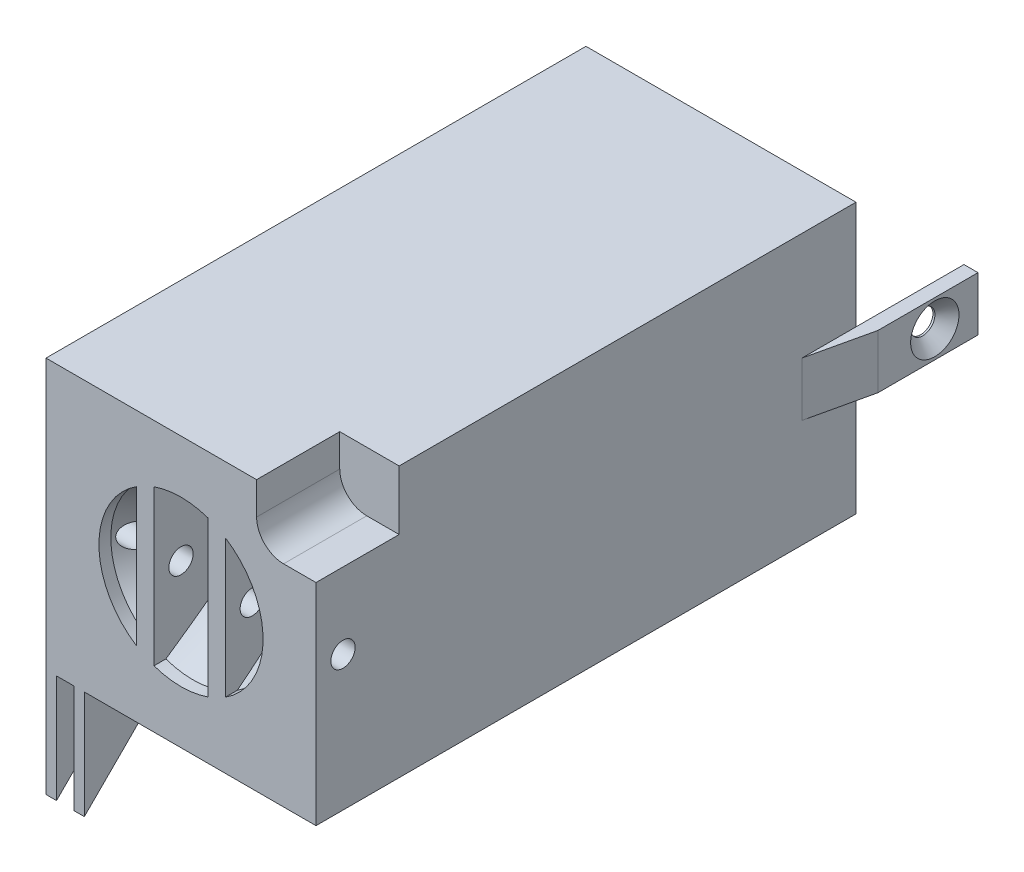
SolidWorks part; units mm, degrees
ref_plane "Alzado" through (0, 0, 0) normal (0, 0, 1) x (1, 0, 0)
ref_plane "Planta" through (0, 0, 0) normal (0, 1, 0) x (1, 0, 0)
ref_plane "Vista lateral" through (0, 0, 0) normal (1, 0, 0) x (0, 0, -1)
sketch "Croquis1" plane through (0, 0, 0) normal (0, 0, 1) x (1, 0, 0)
  line L1 (25, -25) -> (-25, -25)
  line L2 (25, -25) -> (25, 25)
  line L3 (25, 25) -> (-25, 25)
  line L4 (-25, -25) -> (-25, 25)
  line L5 (25, -25) -> (-25, 25) construction
  line L6 (25, 25) -> (-25, -25) construction
  circle A0 centre (0, 0) radius 2
  point P0 (0, 0)
  dimension "D3" = 4
  dimension "D1" = 50
  dimension "D2" = 50
extrude "Saliente-Extruir2" add sketch "Croquis1" along normal blind 100
ref_plane "Plano1" through (0, 0, 0) normal (1, 0, 0) x (0, 0, -1)
sketch "Croquis2" plane through (0, 0, 0) normal (1, 0, 0) x (0, 0, -1)
  line L1 (-100, 25) -> (-100, -25) construction
  line L4 (-100, 15.2) -> (-100, 0)
  line L6 (-97.8, 15.2) -> (-89.8, 10)
  line L7 (-100, 15.2) -> (-97.8, 15.2)
  line L8 (-89.8, 0) -> (-89.8, 10)
  line L9 (-100, 0) -> (-89.8, 0)
  dimension "D1" = 2.2
  dimension "D2" = 10.2
  dimension "D3" = 10
  dimension "D4" = 15.2
revolve "Cortar-Revolución1" cut sketch "Croquis2" angle 360 about L9
sketch "Croquis4" plane through (0, 0, 100) normal (0, 0, 1) x (1, 0, 0)
  line L0 (0, -0.44) -> (0, 0.44) construction
  line L1 (-8.2, 20) -> (-5, 20)
  line L2 (-8.2, 20) -> (-8.2, -20)
  line L3 (-8.2, -20) -> (-5, -20)
  line L4 (-5, 20) -> (-5, -20)
  line L5 (8.2, -20) -> (5, -20)
  line L6 (5, 20) -> (5, -20)
  line L7 (8.2, 20) -> (5, 20)
  line L8 (8.2, 20) -> (8.2, -20)
  point P6 (-5, 0)
  dimension "D1" = 3.2
  dimension "D2" = 5
  dimension "D3" = 40
extrude "Saliente-Extruir5" add sketch "Croquis4" along direction (0, 0, 1) on the side against the normal up to surface (10.2 mm away) up to face at (0, -2, 89.8)
sketch "Croquis8" plane through (0, 0, 89.8) normal (0, 0, 1) x (1, 0, 0)
  circle A0 centre (0, 0) radius 4
  dimension "D1" = 8
extrude "Cortar-Extruir3" cut sketch "Croquis8" against normal offset from surface (87.4 mm away) 2.4 up to face at (0, 0, 0)
sketch "Croquis7" plane through (-25, 0, 0) normal (-1, 0, 0) x (0, 0, 1)
  line L1 (100, 25) -> (100, -25) construction
  circle A0 centre (95, 0) radius 2
  dimension "D1" = 4
  dimension "D2" = 5
extrude "Cortar-Extruir2" cut sketch "Croquis7" against normal up to vertex (50 mm away) up to point (25, -25, 100)
hole_wizard "Refrentado para tornillo tapón con cabeza plana de clavija de M41" positions "Croquis10" profile "Croquis11" countersink size "M4" standard "Ansi Metric" end condition through all
sketch "Croquis10" plane through (-25, 0, 0) normal (-1, 0, 0) x (0, 0, 1)
  point P0 (95, 0)
sketch "Croquis11" plane through (-25, 0, 95) normal (0, 1, 0) x (0, 0, 1)
  line L0 (0, 0) -> (0, 50)
  line L1 (0, 50) -> (2.25, 50)
  line L2 (2.25, 50) -> (2.25, 2.23)
  line L3 (2.25, 2.23) -> (4.48, 0)
  line L5 (4.48, 0) -> (0, 0)
  line L6 (-2.25, 2.23) -> (-4.48, 0) construction
  line L11 (0, -6.35) -> (0, 107.95) construction
  dimension "Diámetro de taladro hasta el siguiente" = 4.5
  dimension "Profundidad de taladro hasta el siguiente" = 50
  dimension "Diámetro de avellanado cercano" = 8.96
  dimension "Ángulo de avellanado cercano" = 90
sketch "Croquis12" plane through (-25, 0, 0) normal (-1, 0, 0) x (0, 0, 1)
  line L1 (100, -25) -> (80, -25)
  line L2 (100, 0) -> (0, 0) construction
  line L5 (100, 25) -> (100, -25) construction
  line L6 (0, 25) -> (0, -25) construction
  line L10 (100, -25) -> (100, -45)
  line L11 (100, -45) -> (80, -25)
extrude "Saliente-Extruir6" add sketch "Croquis12" against normal blind 1.95
extrude "Saliente-Extruir7" add sketch "Croquis12<2>" against normal blind 1.95 from offset 5.15 offset against normal yes
sketch "Croquis12<2>" plane through (-25, 0, 0) normal (-1, 0, 0) x (0, 0, 1) same geometry as "Croquis12"
sketch "Croquis13" plane through (0, 0, 100) normal (0, 0, 1) x (1, 0, 0)
  line L0 (25, 25) -> (25, 14)
  line L1 (25, -25) -> (25, 25) construction
  line L2 (25, 14) -> (19, 14)
  line L3 (14, 19) -> (14, 25)
  line L4 (25, 25) -> (-25, 25) construction
  line L5 (14, 25) -> (25, 25)
  line L6 (25, 25) -> (19.8028, 19.8028) construction
  arc A0 (19, 14) -> (14, 19) centre (19, 19) cw
  dimension "D3" = 5
  dimension "D1" = 11
  dimension "D2" = 11
  dimension "D4" = 45
  dimension "D5" = 7.35
extrude "Cortar-Extruir4" cut sketch "Croquis13" against normal blind 15.4
sketch "Croquis14" plane through (0, -25, 0) normal (0, -1, 0) x (1, 0, 0)
  line L0 (25, 0) -> (25, 10)
  line L1 (25, 100) -> (25, 0) construction
  line L2 (25, 10) -> (27.6, -1.4692)
  line L3 (27.6, -1.4692) -> (27.6, -20)
  line L4 (27.6, -20) -> (25, -20)
  line L5 (25, -20) -> (25, 0)
  dimension "D1" = 20
  dimension "D2" = 10
  dimension "D3" = 2.6
extrude "Saliente-Extruir8" add sketch "Croquis14" along normal blind 5 and the other way blind 5 from offset 25 separate body offset against normal yes
sketch "Croquis15" plane through (27.6, 0, 0) normal (1, 0, 0) x (0, 0, -1)
  line L0 (20, 5) -> (20, -5) construction
  circle A0 centre (12, 0) radius 2.25
  dimension "D1" = 4.5
  dimension "D2" = 8
extrude "Cortar-Extruir5" cut sketch "Croquis15" against normal up to vertex (2.6 mm away) up to point (25, -5, -20)
hole_wizard "Refrentado para tornillo tapón con cabeza plana de clavija de M42" positions "Croquis16" profile "Croquis17" countersink size "M4" standard "Ansi Metric" end condition through all
sketch "Croquis16" plane through (27.6, 0, 0) normal (1, 0, 0) x (0, 0, -1)
  point P0 (12, 0)
sketch "Croquis17" plane through (27.6, 0, -12) normal (0, 1, 0) x (0, 0, -1)
  line L0 (0, 0) -> (0, 52.6)
  line L1 (0, 52.6) -> (2.25, 52.6)
  line L2 (2.25, 52.6) -> (2.25, 2.23)
  line L3 (2.25, 2.23) -> (4.48, 0)
  line L5 (4.48, 0) -> (0, 0)
  line L6 (-2.25, 2.23) -> (-4.48, 0) construction
  line L11 (0, -6.35) -> (0, 107.95) construction
  dimension "Diámetro de taladro hasta el siguiente" = 4.5
  dimension "Profundidad de taladro hasta el siguiente" = 52.6
  dimension "Diámetro de avellanado cercano" = 8.96
  dimension "Ángulo de avellanado cercano" = 90
sketch "Croquis18" plane through (25, 0, 0) normal (1, 0, 0) x (0, 0, -1)
  line L0 (0, -25) -> (20, -25)
  line L1 (20, -25) -> (20, -27.6)
  line L2 (20, -27.6) -> (0.681, -27.6)
  line L3 (0.681, -27.6) -> (-10, -25)
  line L4 (-100, -25) -> (0, -25) construction
  line L5 (-10, -25) -> (0, -25)
  dimension "D1" = 10
  dimension "D2" = 20
  dimension "D3" = 2.6
extrude "Saliente-Extruir9" add sketch "Croquis18" along normal blind 5 and the other way blind 5 from offset 25 offset against normal yes
sketch "Croquis19" plane through (0, -27.6, 0) normal (0, -1, 0) x (1, 0, 0)
  line L0 (-5, -20) -> (5, -20) construction
  circle A0 centre (0, -12) radius 2.25
  dimension "D1" = 4.5
  dimension "D2" = 8
extrude "Cortar-Extruir6" cut sketch "Croquis19" against normal up to vertex (2.6 mm away) up to point (5, -25, -20)
hole_wizard "Refrentado para tornillo tapón con cabeza plana de clavija de M43" positions "Croquis20" profile "Croquis21" countersink size "M4" standard "Ansi Metric" end condition through all
sketch "Croquis20" plane through (0, -27.6, 0) normal (0, -1, 0) x (-1, 0, 0)
  point P0 (0, 12)
sketch "Croquis21" plane through (0, -27.6, -12) normal (1, 0, 0) x (0, 0, -1)
  line L0 (0, 0) -> (0, 52.6)
  line L1 (0, 52.6) -> (2.25, 52.6)
  line L2 (2.25, 52.6) -> (2.25, 2.23)
  line L3 (2.25, 2.23) -> (4.48, 0)
  line L5 (4.48, 0) -> (0, 0)
  line L6 (-2.25, 2.23) -> (-4.48, 0) construction
  line L11 (0, -6.35) -> (0, 107.95) construction
  dimension "Diámetro de taladro hasta el siguiente" = 4.5
  dimension "Profundidad de taladro hasta el siguiente" = 52.6
  dimension "Diámetro de avellanado cercano" = 8.96
  dimension "Ángulo de avellanado cercano" = 90
